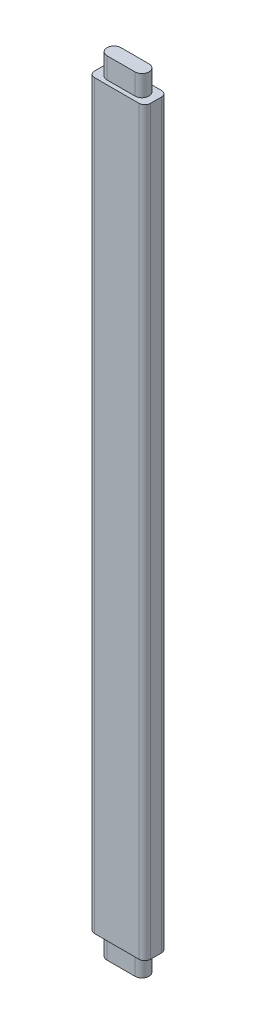
SolidWorks part; units mm, degrees
ref_plane "Front" through (0, 0, 0) normal (0, 0, 1) x (1, 0, 0)
ref_plane "Top" through (0, 0, 0) normal (0, 1, 0) x (1, 0, 0)
ref_plane "Right" through (0, 0, 0) normal (1, 0, 0) x (0, 0, -1)
sketch "Esquisse1" plane through (0, 0, 0) normal (0, 1, 0) x (1, 0, 0)
  line L1 (0, 0) -> (40, 0)
  line L2 (0, 0) -> (0, 16)
  line L3 (0, 16) -> (40, 16)
  line L4 (40, 0) -> (40, 16)
  dimension "D1" = 40
  dimension "D2" = 16
extrude "Boss.-Extru.1" add sketch "Esquisse1" along normal blind 530
sketch "Esquisse2" plane through (0, 530, 0) normal (0, 1, 0) x (1, 0, 0)
  line L0 (40, 8) -> (0, 8) construction
  line L1 (40, 0) -> (40, 16) construction
  line L2 (0, 16) -> (0, 0) construction
  line L3 (10, 8) -> (30, 8) construction
  line L4 (10, 13) -> (30, 13)
  line L5 (10, 3) -> (30, 3)
  arc A0 (10, 13) -> (10, 3) centre (10, 8) ccw
  arc A1 (30, 3) -> (30, 13) centre (30, 8) ccw
  point P8 (20, 8)
  dimension "D1" = 10
  dimension "D2" = 20
extrude "Boss.-Extru.2" add sketch "Esquisse2" along normal blind 15
extrude "Boss.-Extru.3" add sketch "Esquisse2<2>" against normal blind 15 from vertex starting at point (40, 0, 0)
sketch "Esquisse2<2>" plane through (0, 530, 0) normal (0, 1, 0) x (1, 0, 0) same geometry as "Esquisse2"
fillet "Congé1" radius 4 4 edges at (40, 265, 0) (40, 265, -16) (0, 265, -16) (0, 265, 0)
